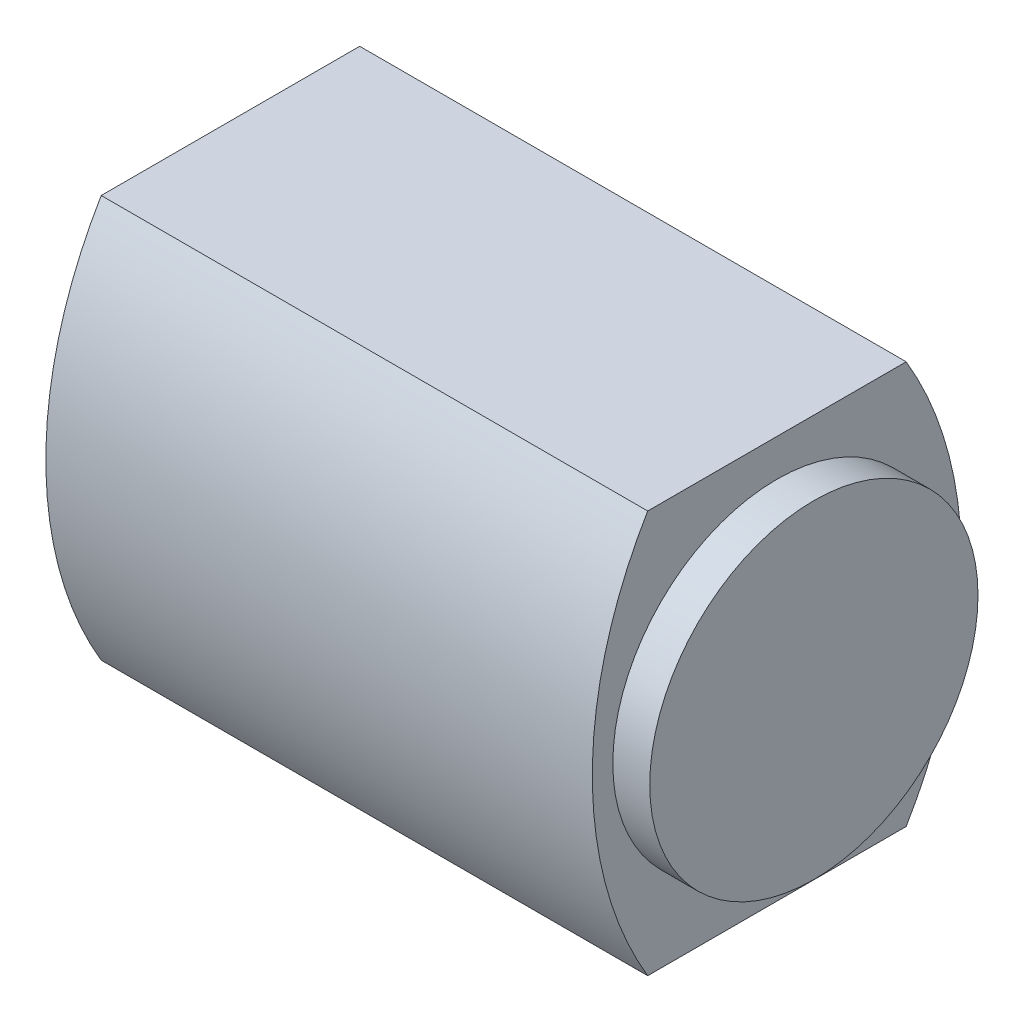
SolidWorks part; units mm, degrees
ref_plane "Front Plane" through (0, 0, 0) normal (0, 0, 1) x (1, 0, 0)
ref_plane "Top Plane" through (0, 0, 0) normal (0, 1, 0) x (1, 0, 0)
ref_plane "Right Plane" through (0, 0, 0) normal (1, 0, 0) x (0, 0, -1)
sketch "Sketch1" plane through (0, 0, 0) normal (1, 0, 0) x (0, 0, 1)
  line L0 (0, 0) -> (-50, 0) construction
  line L2 (-35, -54.5) -> (35, -54.5)
  line L4 (-35, 54.5) -> (35, 54.5)
  line L5 (-35, -54.5) -> (35, 54.5) construction
  line L6 (35, -54.5) -> (-35, 54.5) construction
  line L7 (0, 0) -> (60.7012, 0) construction
  line L8 (50, -54.5) -> (50, 54.5) construction
  arc A0 (-35, -54.5) -> (-35, 54.5) centre (56.5083, 0) cw
  arc A1 (35, -54.5) -> (35, 54.5) centre (-56.5083, 0) ccw
  point P0 (0, 0)
ref_plane "Plane2" through (148, 0, 0) normal (1, 0, 0) x (0, 0, -1)
sketch "Sketch5" plane through (148, 148, 0) normal (1, 0, 0) x (0, -1, 0)
  line L0 (148, 0) -> (148, 50) construction
  line L2 (93.5, 35) -> (93.5, -35)
  line L4 (202.5, 35) -> (202.5, -35)
  line L5 (93.5, 35) -> (202.5, -35) construction
  line L6 (93.5, -35) -> (202.5, 35) construction
  line L7 (148, 0) -> (148, -60.7012) construction
  line L8 (93.5, -50) -> (202.5, -50) construction
  arc A0 (93.5, 35) -> (202.5, 35) centre (148, -56.5083) cw
  arc A1 (93.5, -35) -> (202.5, -35) centre (148, 56.5083) ccw
  point P0 (148, 0)
sketch "Sketch6" plane through (148, 0, 0) normal (1, 0, 0) x (0, 0, -1)
  circle A0 centre (0, 0) radius 44.45
loft "Loft3" add profiles "Sketch1", "Sketch5" connector at (0, 54.5, -35) connector at (148, 54.5, -35)
extrude "Boss-Extrude3" add sketch "Sketch6" along normal blind 10
ref_point "Point3"
ref_axis "Axis1" through (158, 0, 0) along (-1, 0, 0)
